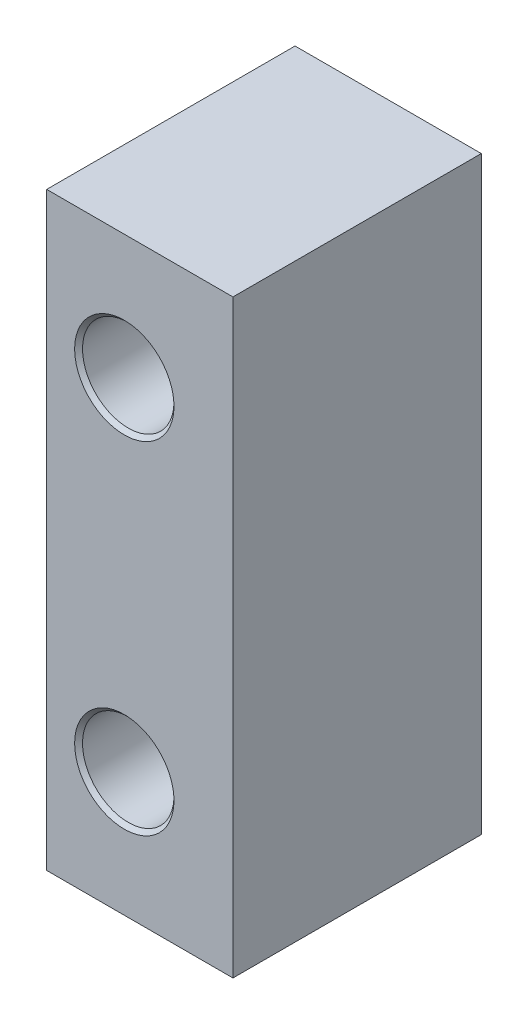
SolidWorks part; units mm, degrees
material "2024-T4"
ref_plane "Front" through (0, 0, 0) normal (0, 0, 1) x (1, 0, 0)
ref_plane "Top" through (0, 0, 0) normal (0, 1, 0) x (1, 0, 0)
ref_plane "Right" through (0, 0, 0) normal (1, 0, 0) x (0, 0, -1)
sketch "Эскиз1" plane through (0, 0, 0) normal (0, 0, 1) x (1, 0, 0)
  line L1 (-3, -9.5) -> (3, -9.5)
  line L2 (-3, -9.5) -> (-3, 9.5)
  line L3 (-3, 9.5) -> (3, 9.5)
  line L4 (3, -9.5) -> (3, 9.5)
  line L5 (-3, -9.5) -> (3, 9.5) construction
  line L6 (-3, 9.5) -> (3, -9.5) construction
  point P0 (0, 0)
  dimension "D1" = 6
  dimension "D2" = 19
extrude "Бобышка-Вытянуть1" add sketch "Эскиз1" along normal blind 8
hole_wizard "Цековка для  винта с внутренним шестигранником #41" positions "Эскиз3" profile "Эскиз2" counterbore size "#4" standard "Ansi (в дюймах)" end condition through all
sketch "Эскиз3" plane through (0, 0, 0) normal (0, 0, -1) x (-1, 0, 0)
  line L0 (-3, -9.5) -> (-3, 9.5) construction
  line L1 (-3, 9.5) -> (3, 9.5) construction
  point P0 (0.5, 5.5)
  point P1 (0.5, -5.5)
  dimension "D1" = 11
  dimension "D2" = 3.5
  dimension "D3" = 4
sketch "Эскиз2" plane through (-0.5, 5.5, 0) normal (1, 0, 0) x (0, 1, 0)
  line L0 (0, 0) -> (0, 8)
  line L1 (1.4732, 7.873) -> (1.6002, 8)
  line L2 (1.4732, 7.873) -> (1.4732, 2.9718)
  line L3 (1.4732, 2.9718) -> (1.6002, 2.8448)
  line L4 (1.6002, 2.8448) -> (2.7788, 2.8448)
  line L5 (2.7788, 2.8448) -> (2.7788, 0.127)
  line L6 (2.7788, 0.127) -> (2.9058, 0)
  line L7 (2.9058, 0) -> (0, 0)
  line L8 (-2.7788, 0.127) -> (-2.9058, 0) construction
  line L9 (-1.4732, 2.9718) -> (-1.6002, 2.8448) construction
  line L11 (0, -6.35) -> (0, 107.95) construction
  line L12 (1.6002, 8) -> (0, 8)
  line L13 (-1.4732, 7.873) -> (-1.6002, 8) construction
  dimension "Диаметр сквозного отверстия" = 2.9464
  dimension "Глубина сквозного отверстия" = 8
  dimension "Диаметр цековки" = 5.5575
  dimension "Глубина цековки" = 2.8448
  dimension "Диаметр передней зенковки" = 5.8115
  dimension "Угол передней зенковки" = 90
  dimension "Диаметр средней зенковки" = 3.2004
  dimension "Угол средней зенковки" = 90
  dimension "Диаметр задней зенковки" = 3.2004
  dimension "Угол задней зенковки" = 90
chamfer "Фаска1" distance 0.5 angle 64 4 edges at (-3, -4.2869, 1.4859) (-3, -6.7131, 1.4859) (-3, 4.2869, 1.4859) (-3, 6.7131, 1.4859) first distance on face at (-0.3606, -5.5, 1.4859) first distance on face at (-0.3606, 5.5, 1.4859)
